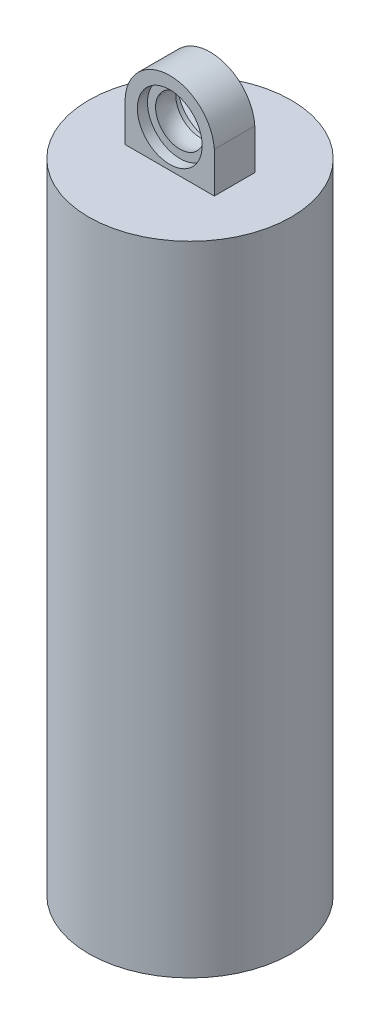
SolidWorks part; units mm, degrees
ref_plane "前视基准面" through (0, 0, 0) normal (0, 0, 1) x (1, 0, 0)
ref_plane "上视基准面" through (0, 0, 0) normal (0, 1, 0) x (1, 0, 0)
ref_plane "右视基准面" through (0, 0, 0) normal (1, 0, 0) x (0, 0, -1)
sketch "草图1" plane through (0, 0, 0) normal (0, 1, 0) x (1, 0, 0)
  circle A0 centre (0, 0) radius 25
  dimension "D1" = 50
extrude "凸台-拉伸1" add sketch "草图1" along normal blind 157.5
sketch "草图2" plane through (0, 0, 0) normal (0, -1, 0) x (1, 0, 0)
  circle A0 centre (0, 0) radius 12.5
  dimension "D1" = 25
extrude "凸台-拉伸2" add sketch "草图2" along normal blind 6
sketch "草图3" plane through (0, -6, 0) normal (0, -1, 0) x (1, 0, 0)
  circle A0 centre (0, 0) radius 6
  dimension "D1" = 12
extrude "切除-拉伸1" cut sketch "草图3" against normal blind 80
sketch "草图4" plane through (0, 0, 0) normal (0, 0, 1) x (1, 0, 0)
  line L0 (25, 157.5) -> (-25, 157.5) construction
  line L1 (-11, 157.5) -> (11, 157.5)
  line L2 (-11, 157.5) -> (-11, 167.5)
  line L4 (11, 157.5) -> (11, 167.5)
  line L5 (0, 193.283) -> (0, 138.3299) construction
  arc A0 (-11, 167.5) -> (11, 167.5) centre (0, 166.7613) cw
  circle A1 centre (0, 166.7613) radius 8
  dimension "D4" = 16
  dimension "D1" = 22
  dimension "D2" = 11
  dimension "D3" = 10
extrude "凸台-拉伸3" add sketch "草图4" against normal mid plane 10
sketch "草图5" plane through (0, 0, 0) normal (0, 0, 1) x (1, 0, 0)
  circle A0 centre (0, 166.7613) radius 8
extrude "凸台-拉伸4" add sketch "草图5" along normal mid plane 5
ref_plane "基准面4" through (0, 0, 4.5) normal (0, 0, 1) x (1, 0, 0)
sketch "草图7" plane through (0, 0, 2.5) normal (0, 0, 1) x (1, 0, 0)
  circle A0 centre (0, 166.7613) radius 6
  dimension "D1" = 12
sketch "草图8" plane through (0, 0, 4.5) normal (0, 0, 1) x (1, 0, 0)
  circle A0 centre (0, 166.7613) radius 4
  dimension "D1" = 8
loft "放样1" add profiles "草图8", "草图7" connector at (2.3572, 163.5297, 4.5) connector at (4.6399, 162.9572, 2.5)
mirror "镜向1" about plane through (0, 0, 0) normal (0, 0, 1) of "放样1"
sketch "草图9" plane through (0, 0, 4.5) normal (0, 0, 1) x (1, 0, 0)
  circle A0 centre (0, 166.7613) radius 2.5
  dimension "D1" = 5
extrude "切除-拉伸2" cut sketch "草图9" against normal blind 31
sketch "草图10" plane through (0, 0, 4.5) normal (0, 0, 1) x (1, 0, 0)
  circle A0 centre (0, 166.7613) radius 6
extrude "切除-拉伸3" cut sketch "草图10" against normal blind 17
sketch "草图11" plane through (0, 0, 0) normal (0, 0, 1) x (1, 0, 0)
  line L0 (0, 173.2613) -> (0, 160.2613)
  arc A0 (0, 160.2613) -> (0, 173.2613) centre (0, 166.7613) ccw
  dimension "D1" = 13
revolve "切除-旋转1" cut sketch "草图11" angle 360 about L0
